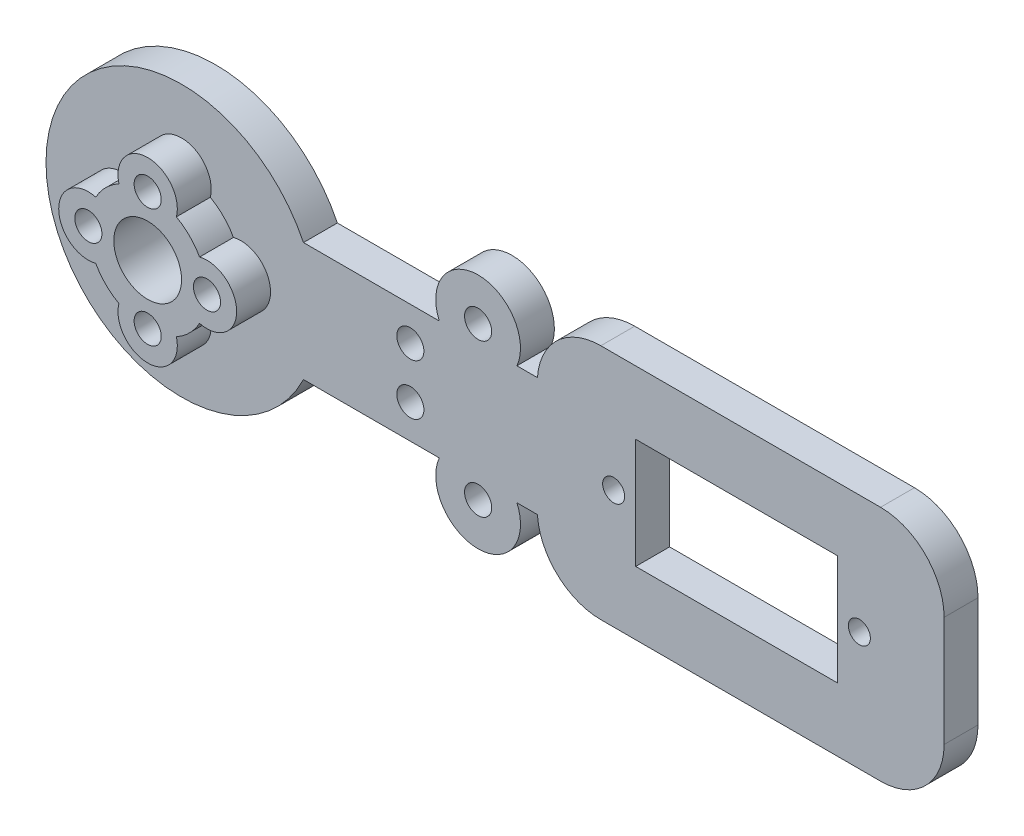
SolidWorks part; units mm, degrees
ref_plane "Front Plane" through (0, 0, 0) normal (0, 0, 1) x (1, 0, 0)
ref_plane "Top Plane" through (0, 0, 0) normal (0, 1, 0) x (1, 0, 0)
ref_plane "Right Plane" through (0, 0, 0) normal (1, 0, 0) x (0, 0, -1)
sketch "Main_web_profile" plane through (0, 0, 0) normal (0, 0, 1) x (1, 0, 0)
  line L1 (0, -7) -> (60, -7)
  line L2 (0, -7) -> (0, 7)
  line L3 (0, 7) -> (60, 7)
  line L4 (60, -7) -> (60, 7)
  dimension "D1" = 60
  dimension "D2" = 14
  dimension "D3" = 7
extrude "Main_web" add sketch "Main_web_profile" along normal blind 4
sketch "Shoulder_horn_flange_profile" plane through (0, 0, 0) normal (0, 0, 1) x (1, 0, 0)
  circle A0 centre (0, 0) radius 16
  dimension "D1" = 32
extrude "Shoulder_horn_flange" add sketch "Shoulder_horn_flange_profile" along normal blind 4
sketch "Elbow_servo_mount_profile" plane through (0, 0, 0) normal (0, 0, 1) x (1, 0, 0)
  line L1 (42, -14) -> (90, -14)
  line L2 (42, -14) -> (42, 14)
  line L3 (42, 14) -> (90, 14)
  line L4 (90, -14) -> (90, 14)
  dimension "D1" = 48
  dimension "D2" = 28
  dimension "D3" = 42
  dimension "D4" = 14
extrude "Elbow_servo_mount" add sketch "Elbow_servo_mount_profile" along normal blind 4
sketch "SG90_body_clearance_profile" plane through (0, 0, 0) normal (0, 0, 1) x (1, 0, 0)
  line L1 (53.6, -6.5) -> (77.4, -6.5)
  line L2 (53.6, -6.5) -> (53.6, 6.5)
  line L3 (53.6, 6.5) -> (77.4, 6.5)
  line L4 (77.4, -6.5) -> (77.4, 6.5)
  dimension "D1" = 23.8
  dimension "D2" = 13
  dimension "D3" = 53.6
  dimension "D4" = 6.5
extrude "SG90_body_clearance" cut sketch "SG90_body_clearance_profile" along normal through all from offset 5 offset against normal yes
sketch "Elbow_tab_fasteners_profile" plane through (0, 0, 0) normal (0, 0, 1) x (1, 0, 0)
  circle A0 centre (51, 0) radius 1.3
  circle A1 centre (80, 0) radius 1.3
  dimension "D1" = 2.6
  dimension "D2" = 2.6
  dimension "D3" = 51
  dimension "D4" = 80
extrude "Elbow_tab_fasteners" cut sketch "Elbow_tab_fasteners_profile" along normal through all from offset 50 offset against normal yes
sketch "Shoulder_center_screw_access_profile" plane through (0, 0, 0) normal (0, 0, 1) x (1, 0, 0)
  circle A0 centre (0, 0) radius 4
  dimension "D1" = 8
extrude "Shoulder_center_screw_access" cut sketch "Shoulder_center_screw_access_profile" along normal through all from offset 50 offset against normal yes
sketch "Cable_tie_holes_profile" plane through (0, 0, 0) normal (0, 0, 1) x (1, 0, 0)
  circle A0 centre (27, -3) radius 1.6
  circle A1 centre (27, 3) radius 1.6
  dimension "D1" = 3.2
  dimension "D2" = 3.2
  dimension "D3" = 27
  dimension "D4" = 3
  dimension "D5" = 3
extrude "Cable_tie_holes" cut sketch "Cable_tie_holes_profile" along normal through all from offset 50 offset against normal yes
sketch "Passive_lower_mount_boss_profile" plane through (0, 0, 0) normal (0, 0, 1) x (1, 0, 0)
  circle A0 centre (35, -9) radius 5
  dimension "D1" = 10
  dimension "D2" = 35
  dimension "D3" = 9
extrude "Passive_lower_mount_boss" add sketch "Passive_lower_mount_boss_profile" along normal blind 4
sketch "Passive_upper_mount_boss_profile" plane through (0, 0, 0) normal (0, 0, 1) x (1, 0, 0)
  circle A0 centre (35, 9) radius 5
  dimension "D1" = 10
  dimension "D2" = 35
  dimension "D3" = 9
extrude "Passive_upper_mount_boss" add sketch "Passive_upper_mount_boss_profile" along normal blind 4
sketch "Passive_cheek_standoffs_profile" plane through (0, 0, 0) normal (0, 0, 1) x (1, 0, 0)
  circle A0 centre (35, -9) radius 1.6
  circle A1 centre (35, 9) radius 1.6
  dimension "D1" = 3.2
  dimension "D2" = 3.2
  dimension "D3" = 35
  dimension "D4" = 9
  dimension "D5" = 9
extrude "Passive_cheek_standoffs" cut sketch "Passive_cheek_standoffs_profile" along normal through all from offset 50 offset against normal yes
sketch "Shoulder_dowel_support_hub_profile" plane through (0, 0, 0) normal (0, 0, 1) x (1, 0, 0)
  circle A0 centre (0, 0) radius 7
  circle A1 centre (0, 0) radius 4
  dimension "D1" = 14
  dimension "D2" = 8
extrude "Shoulder_dowel_support_hub" add sketch "Shoulder_dowel_support_hub_profile" along normal blind 4 from offset 4
sketch "Raised_M3_washer_seats_PCD14_profile" plane through (0, 0, 0) normal (0, 0, 1) x (1, 0, 0)
  circle A0 centre (7, 0) radius 3.5
  circle A1 centre (-7, 0) radius 3.5
  circle A2 centre (0, 7) radius 3.5
  circle A3 centre (0, -7) radius 3.5
  dimension "D1" = 7
  dimension "D2" = 7
  dimension "D3" = 7
  dimension "D4" = 7
  dimension "D5" = 7
  dimension "D6" = 7
  dimension "D7" = 7
  dimension "D8" = 7
extrude "Raised_M3_washer_seats_height8" add sketch "Raised_M3_washer_seats_PCD14_profile" along normal blind 4 from offset 4
sketch "Metal_horn_M3_clearance_PCD14_profile" plane through (0, 0, 0) normal (0, 0, 1) x (1, 0, 0)
  circle A0 centre (7, 0) radius 1.6
  circle A1 centre (-7, 0) radius 1.6
  circle A2 centre (0, 7) radius 1.6
  circle A3 centre (0, -7) radius 1.6
  dimension "D1" = 3.2
  dimension "D2" = 3.2
  dimension "D3" = 3.2
  dimension "D4" = 3.2
  dimension "D5" = 7
  dimension "D6" = 7
  dimension "D7" = 7
  dimension "D8" = 7
extrude "Metal_horn_M3_clearance_PCD14" cut sketch "Metal_horn_M3_clearance_PCD14_profile" along normal through all from offset 50 offset against normal yes
sketch "Restore_shoulder_sleeve_bore_profile" plane through (0, 0, 0) normal (0, 0, 1) x (1, 0, 0)
  circle A0 centre (0, 0) radius 4
  dimension "D1" = 8
extrude "Restore_shoulder_sleeve_bore" cut sketch "Restore_shoulder_sleeve_bore_profile" along normal through all from offset 50 offset against normal yes
fillet "Fillet1" radius 7.5 4 edges at (42, -14, 2) (90, -14, 2) (90, 14, 2) (42, 14, 2)
